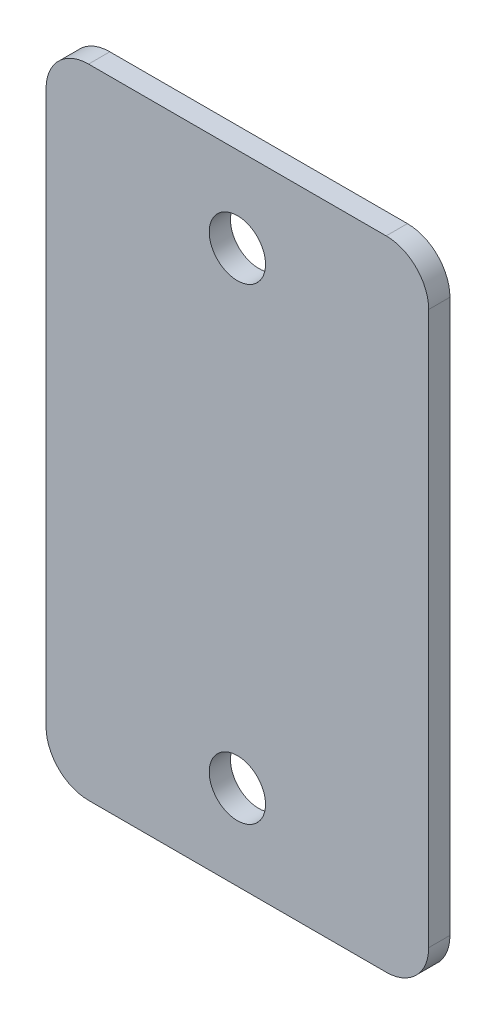
SolidWorks part; units mm, degrees
material "ABS"
ref_plane "Front Plane" through (0, 0, 0) normal (0, 0, 1) x (1, 0, 0)
ref_plane "Top Plane" through (0, 0, 0) normal (0, 1, 0) x (1, 0, 0)
ref_plane "Right Plane" through (0, 0, 0) normal (1, 0, 0) x (0, 0, -1)
sketch "Sketch1" plane through (0, 0, 0) normal (0, 0, 1) x (1, 0, 0)
  line L0 (0, 0) -> (18, 0) construction
  line L1 (-18, -30) -> (18, -30)
  line L2 (-18, -30) -> (-18, 30)
  line L3 (-18, 30) -> (18, 30)
  line L4 (18, -30) -> (18, 30)
  line L5 (-18, -30) -> (18, 30) construction
  line L6 (-18, 30) -> (18, -30) construction
  point P0 (0, 0)
  point P6 (0, 22)
  point P9 (0, -22)
  dimension "D1" = 36
  dimension "D2" = 60
  dimension "D3" = 8
extrude "Boss-Extrude1" add sketch "Sketch1" along normal mid plane 2
hole_wizard "M5 Clearance Hole1" positions "Sketch2" profile "Sketch3" hole size "M5" standard "ANSI Metric" end condition through all
sketch "Sketch2" plane through (0, 0, 1) normal (0, 0, 1) x (1, 0, 0)
  point P0 (0, 22)
  point P3 (0, -22)
sketch "Sketch3" plane through (0, 22, 1) normal (1, 0, 0) x (0, -1, 0)
  line L0 (0, 0) -> (0, 2)
  line L1 (0, 2) -> (2.65, 2)
  line L2 (2.65, 2) -> (2.65, 0)
  line L5 (2.65, 0) -> (0, 0)
  line L11 (0, -6.35) -> (0, 107.95) construction
  dimension "Thru Hole Dia." = 5.3
  dimension "Thru Hole Depth" = 2
fillet "Fillet1" radius 4 4 edges at (18, -30, 0) (-18, -30, 0) (18, 30, 0) (-18, 30, 0)
